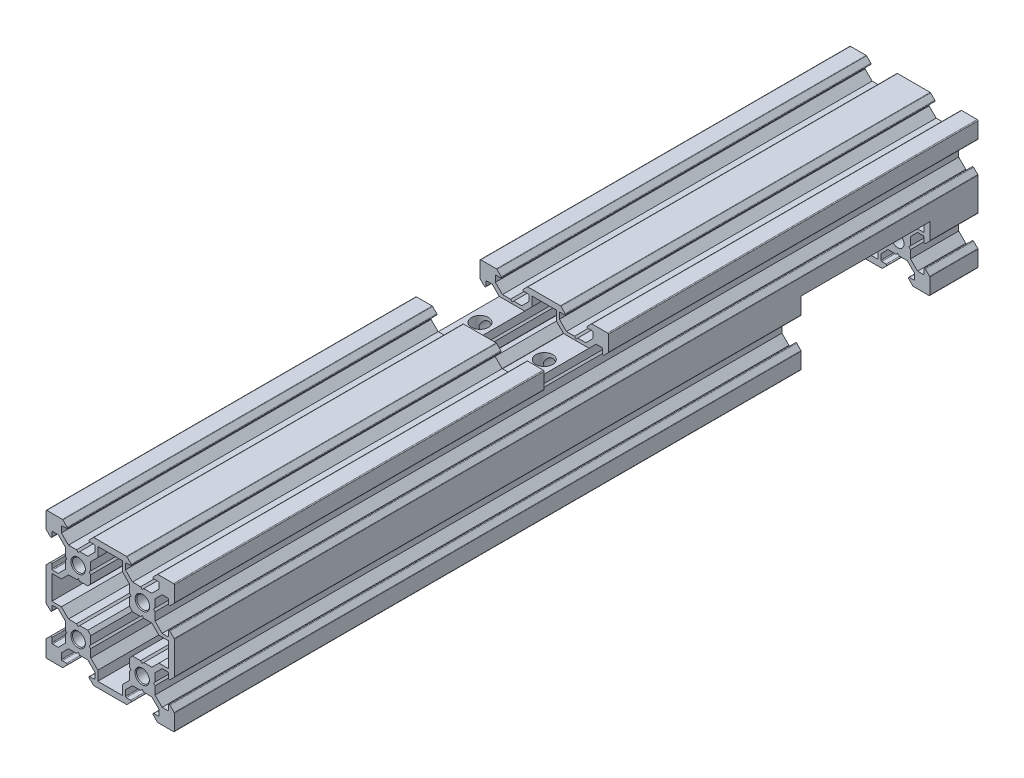
SolidWorks part; units mm, degrees
other "Marca1"
sketch "Croquis18" plane through (9.9172, 24.3141, -145) normal (0.9987, 0.0504, -0.0013) x (-0.0087, 0.1472, -0.9891)
ref_plane "Alzado" through (0, 0, 0) normal (0, 0, 1) x (1, 0, 0)
ref_plane "Planta" through (0, 0, 0) normal (0, 1, 0) x (1, 0, 0)
ref_plane "Vista lateral" through (0, 0, 0) normal (1, 0, 0) x (0, 0, -1)
sketch "Croquis1" plane through (0, 0, 0) normal (0, 0, 1) x (1, 0, 0)
  line L0 (-25.2101, -6.2) -> (-28.2, -6.2)
  line L1 (-13.8828, 8.2) -> (-6.2, 8.2)
  line L4 (-4.8096, 9.9268) -> (-3.5096, 8.6268)
  line L5 (-3.6864, 8.2) -> (-5.0429, 8.2)
  line L6 (-5.2929, 7.95) -> (-5.2929, 6.2)
  line L13 (-14.8728, 8.2) -> (-16.6, 8.2)
  line L14 (-5.2929, 6.2) -> (-3.0929, 4)
  line L15 (-3.0929, 4) -> (-0.5828, 4)
  line L16 (-16.0828, 0.5) -> (-16.5828, 0)
  line L17 (-16.0828, 3.0101) -> (-16.0828, 0.5)
  line L18 (-13.8828, 5.2101) -> (-16.0828, 3.0101)
  line L19 (-13.8828, 8.2) -> (-13.8828, 5.2101)
  line L23 (-16.0828, -3.0101) -> (-16.0828, -0.5)
  line L24 (-16.0828, -0.5) -> (-16.5828, 0)
  line L29 (-0.5828, 4) -> (-0.0828, 3.5)
  line L30 (-0.0828, 3.5) -> (0.4172, 4)
  line L31 (0.4172, 4) -> (2.9272, 4)
  line L32 (2.9272, 4) -> (5.1272, 6.2)
  line L33 (5.1272, 6.2) -> (5.1272, 7.95)
  line L34 (4.8772, 8.2) -> (3.5207, 8.2)
  line L35 (3.3439, 8.6268) -> (4.6439, 9.9268)
  line L36 (4.8207, 10) -> (9.6672, 10)
  line L37 (9.9172, 9.75) -> (9.9172, 4.9036)
  line L38 (9.8439, 4.7268) -> (8.5439, 3.4268)
  line L39 (8.1172, 3.6036) -> (8.1172, 4.9601)
  line L40 (7.8672, 5.2101) -> (6.1172, 5.2101)
  line L41 (6.1172, 5.2101) -> (3.9172, 3.0101)
  line L42 (3.9172, 3.0101) -> (3.9172, 0.5)
  line L43 (3.9172, 0.5) -> (3.4172, 0)
  line L44 (3.4172, 0) -> (3.9172, -0.5)
  line L45 (3.9172, -0.5) -> (3.9172, -3.0101)
  line L46 (3.9172, -3.0101) -> (6.1172, -5.2101)
  line L47 (6.1172, -5.2101) -> (7.8672, -5.2101)
  line L48 (8.1172, -4.9601) -> (8.1172, -3.6036)
  line L49 (8.5439, -3.4268) -> (9.8439, -4.7268)
  line L55 (5.1272, -6.2) -> (2.9272, -4)
  line L56 (2.9272, -4) -> (0.4172, -4)
  line L57 (0.4172, -4) -> (-0.0828, -3.5)
  line L58 (-0.0828, -3.5) -> (-0.5828, -4)
  line L59 (-0.5828, -4) -> (-3.0929, -4)
  line L66 (-4, -3.0101) -> (-4, -0.5)
  line L67 (-4, -0.5) -> (-3.5, 0)
  line L68 (-4, 0.5) -> (-3.5, 0)
  line L69 (-4, 3.0101) -> (-4, 0.5)
  line L70 (-6.2, 5.2101) -> (-4, 3.0101)
  line L71 (-6.2, 8.2) -> (-6.2, 5.2101)
  line L72 (-16.9899, -4) -> (-16.0828, -3.0101)
  line L78 (-4, -3.0101) -> (-3.0929, -4)
  line L164 (-26.2, 5.2101) -> (-24, 3.0101)
  line L165 (-24, 3.0101) -> (-24, 0.5)
  line L166 (-24, 0.5) -> (-23.5, 0)
  line L167 (-23.5, 0) -> (-24, -0.5)
  line L168 (-24, -0.5) -> (-24, -3.0101)
  line L169 (-24, -3.0101) -> (-26.2, -5.2101)
  line L170 (-26.2, -5.2101) -> (-27.95, -5.2101)
  line L171 (-28.2, -4.9601) -> (-28.2, -3.6036)
  line L172 (-28.6268, -3.4268) -> (-29.9268, -4.7268)
  line L178 (-25.2101, -6.2) -> (-23.0101, -4)
  line L179 (-23.0101, -4) -> (-20.5, -4)
  line L180 (-20.5, -4) -> (-20, -3.5)
  line L181 (-20, -3.5) -> (-19.5, -4)
  line L182 (-19.5, -4) -> (-16.9899, -4)
  line L228 (-4.9864, 10) -> (-15.0964, 10)
  line L229 (-15.2732, 9.9268) -> (-16.5732, 8.6268)
  line L230 (-16.3964, 8.2) -> (-15.0399, 8.2)
  line L231 (-14.7899, 7.95) -> (-14.7899, 6.2)
  line L232 (-14.7899, 6.2) -> (-16.9899, 4)
  line L233 (-16.9899, 4) -> (-19.5, 4)
  line L234 (-19.5, 4) -> (-20, 3.5)
  line L235 (-20, 3.5) -> (-20.5, 4)
  line L236 (-20.5, 4) -> (-23.0101, 4)
  line L237 (-23.0101, 4) -> (-25.2101, 6.2)
  line L238 (-25.2101, 6.2) -> (-25.2101, 7.95)
  line L239 (-24.9601, 8.2) -> (-23.6036, 8.2)
  line L240 (-23.4268, 8.6268) -> (-24.7268, 9.9268)
  line L241 (-24.9036, 10) -> (-29.75, 10)
  line L242 (-30, 9.75) -> (-30, 4.9036)
  line L243 (-29.9268, 4.7268) -> (-28.6268, 3.4268)
  line L244 (-28.2, 3.6036) -> (-28.2, 4.9601)
  line L245 (-27.95, 5.2101) -> (-26.2, 5.2101)
  line L256 (-29.9268, 0) -> (13.1752, 0) construction
  line L257 (-29.75, -19.9172) -> (9.6672, -19.9172) construction
  line L258 (-20, 14.7068) -> (-20, -27.5583) construction
  line L259 (-40.4121, -9.9586) -> (29.5949, -9.9586) construction
  line L260 (-0.0828, 12.632) -> (-0.0828, -27.5583) construction
  line L261 (-10.0414, -36.5607) -> (-10.0414, 12.632) construction
  line L262 (-30, -4.9036) -> (-30, -6.2)
  line L265 (9.9172, -6.2) -> (9.9172, -4.9036)
  line L267 (5.1272, -13.7172) -> (2.9272, -15.9172)
  line L268 (2.9272, -15.9172) -> (0.4172, -15.9172)
  line L269 (0.4172, -15.9172) -> (-0.0828, -16.4172)
  line L270 (-0.0828, -16.4172) -> (-0.5828, -15.9172)
  line L271 (-0.5828, -15.9172) -> (-3.0929, -15.9172)
  line L272 (-4, -16.9071) -> (-3.0929, -15.9172)
  line L273 (-4, -16.9071) -> (-4, -19.4172)
  line L274 (-4, -19.4172) -> (-3.5, -19.9172)
  line L275 (-4, -20.4172) -> (-3.5, -19.9172)
  line L276 (-4, -22.9272) -> (-4, -20.4172)
  line L277 (-6.2, -25.1272) -> (-4, -22.9272)
  line L278 (-6.2, -28.1172) -> (-6.2, -25.1272)
  line L279 (-13.8828, -28.1172) -> (-6.2, -28.1172)
  line L280 (-13.8828, -28.1172) -> (-13.8828, -25.1272)
  line L281 (-13.8828, -25.1272) -> (-16.0828, -22.9272)
  line L282 (-16.0828, -22.9272) -> (-16.0828, -20.4172)
  line L283 (-16.0828, -20.4172) -> (-16.5828, -19.9172)
  line L284 (-16.0828, -19.4172) -> (-16.5828, -19.9172)
  line L285 (-16.0828, -16.9071) -> (-16.0828, -19.4172)
  line L286 (-16.9899, -15.9172) -> (-16.0828, -16.9071)
  line L287 (-19.5, -15.9172) -> (-16.9899, -15.9172)
  line L288 (-20, -16.4172) -> (-19.5, -15.9172)
  line L289 (-20.5, -15.9172) -> (-20, -16.4172)
  line L290 (-23.0101, -15.9172) -> (-20.5, -15.9172)
  line L291 (-25.2101, -13.7172) -> (-23.0101, -15.9172)
  line L292 (-25.2101, -13.7172) -> (-28.2, -13.7172)
  line L294 (-30, -15.0136) -> (-30, -13.7172)
  line L295 (-28.6268, -16.4904) -> (-29.9268, -15.1904)
  line L296 (-28.2, -14.9571) -> (-28.2, -16.3136)
  line L297 (-26.2, -14.7071) -> (-27.95, -14.7071)
  line L298 (-24, -16.9071) -> (-26.2, -14.7071)
  line L299 (-24, -19.4172) -> (-24, -16.9071)
  line L300 (-23.5, -19.9172) -> (-24, -19.4172)
  line L301 (-24, -20.4172) -> (-23.5, -19.9172)
  line L302 (-24, -22.9272) -> (-24, -20.4172)
  line L303 (-26.2, -25.1272) -> (-24, -22.9272)
  line L304 (-27.95, -25.1272) -> (-26.2, -25.1272)
  line L305 (-28.2, -23.5207) -> (-28.2, -24.8772)
  line L306 (-29.9268, -24.6439) -> (-28.6268, -23.3439)
  line L307 (-30, -29.6672) -> (-30, -24.8207)
  line L308 (-24.9036, -29.9172) -> (-29.75, -29.9172)
  line L309 (-23.4268, -28.5439) -> (-24.7268, -29.8439)
  line L310 (-24.9601, -28.1172) -> (-23.6036, -28.1172)
  line L311 (-25.2101, -26.1172) -> (-25.2101, -27.8672)
  line L312 (-23.0101, -23.9172) -> (-25.2101, -26.1172)
  line L313 (-20.5, -23.9172) -> (-23.0101, -23.9172)
  line L314 (-20, -23.4172) -> (-20.5, -23.9172)
  line L315 (-19.5, -23.9172) -> (-20, -23.4172)
  line L316 (-16.9899, -23.9172) -> (-19.5, -23.9172)
  line L317 (-14.7899, -26.1172) -> (-16.9899, -23.9172)
  line L318 (-14.7899, -27.8672) -> (-14.7899, -26.1172)
  line L319 (-16.3964, -28.1172) -> (-15.0399, -28.1172)
  line L320 (-15.2732, -29.8439) -> (-16.5732, -28.5439)
  line L321 (-4.9864, -29.9172) -> (-15.0964, -29.9172)
  line L322 (-4.8096, -29.8439) -> (-3.5096, -28.5439)
  line L323 (-3.6864, -28.1172) -> (-5.0429, -28.1172)
  line L324 (-5.2929, -27.8672) -> (-5.2929, -26.1172)
  line L325 (-5.2929, -26.1172) -> (-3.0929, -23.9172)
  line L326 (-3.0929, -23.9172) -> (-0.5828, -23.9172)
  line L327 (-0.5828, -23.9172) -> (-0.0828, -23.4172)
  line L328 (-0.0828, -23.4172) -> (0.4172, -23.9172)
  line L329 (0.4172, -23.9172) -> (2.9272, -23.9172)
  line L330 (2.9272, -23.9172) -> (5.1272, -26.1172)
  line L331 (5.1272, -26.1172) -> (5.1272, -27.8672)
  line L332 (4.8772, -28.1172) -> (3.5207, -28.1172)
  line L333 (3.3439, -28.5439) -> (4.6439, -29.8439)
  line L334 (4.8207, -29.9172) -> (9.6672, -29.9172)
  line L335 (9.9172, -29.6672) -> (9.9172, -24.8207)
  line L336 (9.8439, -24.6439) -> (8.5439, -23.3439)
  line L337 (8.1172, -23.5207) -> (8.1172, -24.8772)
  line L338 (7.8672, -25.1272) -> (6.1172, -25.1272)
  line L339 (6.1172, -25.1272) -> (3.9172, -22.9272)
  line L340 (3.9172, -22.9272) -> (3.9172, -20.4172)
  line L341 (3.9172, -20.4172) -> (3.4172, -19.9172)
  line L342 (3.4172, -19.9172) -> (3.9172, -19.4172)
  line L343 (3.9172, -19.4172) -> (3.9172, -16.9071)
  line L344 (3.9172, -16.9071) -> (6.1172, -14.7071)
  line L345 (6.1172, -14.7071) -> (7.8672, -14.7071)
  line L346 (8.1172, -14.9571) -> (8.1172, -16.3136)
  line L347 (8.5439, -16.4904) -> (9.8439, -15.1904)
  line L348 (9.9172, -13.7172) -> (9.9172, -15.0136)
  line L349 (5.1272, -13.7172) -> (8.1172, -13.7172)
  line L350 (5.1272, -6.2) -> (8.1172, -6.2)
  line L351 (8.1172, -6.2) -> (8.1172, -13.7172)
  line L352 (9.9172, -13.7172) -> (9.9172, -6.2)
  line L353 (-30, -6.2) -> (-30, -13.7172)
  line L354 (-28.2, -13.7172) -> (-28.2, -6.2)
  arc A0 (-3.5096, 8.6268) -> (-3.6864, 8.2) centre (-3.6864, 8.45) cw
  arc A1 (-15.0964, 10) -> (-15.2732, 9.9268) centre (-15.0964, 9.75) ccw
  arc A2 (-15.0399, 8.2) -> (-14.7899, 7.95) centre (-15.0399, 7.95) cw
  arc A4 (-16.5732, 8.6268) -> (-16.3964, 8.2) centre (-16.3964, 8.45) ccw
  arc A13 (-29.9268, -4.7268) -> (-30, -4.9036) centre (-29.75, -4.9036) ccw
  arc A14 (-28.2, -3.6036) -> (-28.6268, -3.4268) centre (-28.45, -3.6036) ccw
  arc A15 (-27.95, -5.2101) -> (-28.2, -4.9601) centre (-27.95, -4.9601) cw
  arc A16 (-24.7268, 9.9268) -> (-24.9036, 10) centre (-24.9036, 9.75) ccw
  arc A17 (-23.6036, 8.2) -> (-23.4268, 8.6268) centre (-23.6036, 8.45) ccw
  arc A18 (-25.2101, 7.95) -> (-24.9601, 8.2) centre (-24.9601, 7.95) cw
  arc A19 (-28.2, 4.9601) -> (-27.95, 5.2101) centre (-27.95, 4.9601) cw
  arc A20 (-28.6268, 3.4268) -> (-28.2, 3.6036) centre (-28.45, 3.6036) ccw
  arc A21 (-30, 4.9036) -> (-29.9268, 4.7268) centre (-29.75, 4.9036) ccw
  arc A22 (-29.75, 10) -> (-30, 9.75) centre (-29.75, 9.75) ccw
  arc A23 (-5.0429, 8.2) -> (-5.2929, 7.95) centre (-5.0429, 7.95) ccw
  arc A24 (5.1272, 7.95) -> (4.8772, 8.2) centre (4.8772, 7.95) ccw
  arc A25 (3.5207, 8.2) -> (3.3439, 8.6268) centre (3.5207, 8.45) cw
  arc A26 (4.6439, 9.9268) -> (4.8207, 10) centre (4.8207, 9.75) cw
  arc A27 (9.6672, 10) -> (9.9172, 9.75) centre (9.6672, 9.75) cw
  arc A28 (9.9172, 4.9036) -> (9.8439, 4.7268) centre (9.6672, 4.9036) cw
  arc A29 (8.5439, 3.4268) -> (8.1172, 3.6036) centre (8.3672, 3.6036) cw
  arc A30 (8.1172, 4.9601) -> (7.8672, 5.2101) centre (7.8672, 4.9601) ccw
  arc A31 (7.8672, -5.2101) -> (8.1172, -4.9601) centre (7.8672, -4.9601) ccw
  arc A32 (8.1172, -3.6036) -> (8.5439, -3.4268) centre (8.3672, -3.6036) cw
  arc A33 (9.8439, -4.7268) -> (9.9172, -4.9036) centre (9.6672, -4.9036) cw
  arc A41 (-4.9864, 10) -> (-4.8096, 9.9268) centre (-4.9864, 9.75) cw
  arc A42 (-29.9268, -15.1904) -> (-30, -15.0136) centre (-29.75, -15.0136) cw
  arc A43 (-28.2, -16.3136) -> (-28.6268, -16.4904) centre (-28.45, -16.3136) cw
  arc A44 (-27.95, -14.7071) -> (-28.2, -14.9571) centre (-27.95, -14.9571) ccw
  arc A45 (-28.2, -24.8772) -> (-27.95, -25.1272) centre (-27.95, -24.8772) ccw
  arc A46 (-28.6268, -23.3439) -> (-28.2, -23.5207) centre (-28.45, -23.5207) cw
  arc A47 (-30, -24.8207) -> (-29.9268, -24.6439) centre (-29.75, -24.8207) cw
  arc A48 (-29.75, -29.9172) -> (-30, -29.6672) centre (-29.75, -29.6672) cw
  arc A49 (-24.7268, -29.8439) -> (-24.9036, -29.9172) centre (-24.9036, -29.6672) cw
  arc A50 (-23.6036, -28.1172) -> (-23.4268, -28.5439) centre (-23.6036, -28.3672) cw
  arc A51 (-25.2101, -27.8672) -> (-24.9601, -28.1172) centre (-24.9601, -27.8672) ccw
  arc A52 (-15.0399, -28.1172) -> (-14.7899, -27.8672) centre (-15.0399, -27.8672) ccw
  arc A53 (-16.5732, -28.5439) -> (-16.3964, -28.1172) centre (-16.3964, -28.3672) cw
  arc A54 (-15.0964, -29.9172) -> (-15.2732, -29.8439) centre (-15.0964, -29.6672) cw
  arc A55 (-4.9864, -29.9172) -> (-4.8096, -29.8439) centre (-4.9864, -29.6672) ccw
  arc A56 (-3.5096, -28.5439) -> (-3.6864, -28.1172) centre (-3.6864, -28.3672) ccw
  arc A57 (-5.0429, -28.1172) -> (-5.2929, -27.8672) centre (-5.0429, -27.8672) cw
  arc A58 (5.1272, -27.8672) -> (4.8772, -28.1172) centre (4.8772, -27.8672) cw
  arc A59 (3.5207, -28.1172) -> (3.3439, -28.5439) centre (3.5207, -28.3672) ccw
  arc A60 (4.6439, -29.8439) -> (4.8207, -29.9172) centre (4.8207, -29.6672) ccw
  arc A61 (9.6672, -29.9172) -> (9.9172, -29.6672) centre (9.6672, -29.6672) ccw
  arc A62 (9.9172, -24.8207) -> (9.8439, -24.6439) centre (9.6672, -24.8207) ccw
  arc A63 (8.5439, -23.3439) -> (8.1172, -23.5207) centre (8.3672, -23.5207) ccw
  arc A64 (8.1172, -24.8772) -> (7.8672, -25.1272) centre (7.8672, -24.8772) cw
  arc A65 (7.8672, -14.7071) -> (8.1172, -14.9571) centre (7.8672, -14.9571) cw
  arc A66 (8.1172, -16.3136) -> (8.5439, -16.4904) centre (8.3672, -16.3136) ccw
  arc A67 (9.8439, -15.1904) -> (9.9172, -15.0136) centre (9.6672, -15.0136) ccw
  point P134 (-10.0414, 8.2)
  dimension "D1" = 0.25
  dimension "D2" = 7.6828
  dimension "D3" = 10.1101
  dimension "D4" = 19.9172
  dimension "D5" = 19.9172
  dimension "D6" = 9.9586
  dimension "D7" = 9.9586
extrude "Saliente-Extruir1" add sketch "Croquis1" along normal blind 125 and the other way blind 125 contours A41 L228 L1 L71 L70 L69 L68 L67 L66 L23 L24 L16 L17 L18 L19 A1 L229 A4 L13 A2 L231 L232 L233 L234 L235 L236 L237 L238 A18 L239 A17 L240 A16 L241 A22 L242 A21 L243 A20 L244 region at (-4.5588, 8.8776, 0)
sketch "Croquis4" plane through (0, 0, 125) normal (0, 0, 1) x (1, 0, 0)
  line L0 (-24.6708, 0) -> (6.8007, 0) construction
  line L1 (-20, 3.5) -> (-20, 0) construction
  line L2 (-24.6708, -19.9172) -> (-20, -19.9172) construction
  line L3 (-20, -19.9172) -> (-20, -16.4172) construction
  line L4 (-0.0828, -16.4172) -> (-0.0828, -19.9172) construction
  line L5 (-0.0828, -19.9172) -> (3.4172, -19.9172) construction
  circle A0 centre (-20, 0) radius 2
  circle A1 centre (0, 0) radius 2
  circle A2 centre (-0.0828, -19.9172) radius 2
  circle A3 centre (-20, -19.9172) radius 2
  dimension "D1" = 4
extrude "Cortar-Extruir1" cut sketch "Croquis4" against normal through all
chamfer "Chaflán1" distance 0.25 angle 45 8 edges at (-18, 0, -125) (-18, -19.9172, -125) (2, 0, -125) (1.9172, -19.9172, -125) (1.9172, -19.9172, 125) (2, 0, 125) (-18, 0, 125) (-18, -19.9172, 125)
sketch "Croquis19" plane through (-30, 0, 0) normal (-1, 0, 0) x (0, 0, 1)
  line L0 (-110, -29.9172) -> (-110, -9.9172)
  line L1 (-110, -9.9172) -> (-70, -9.9172)
  line L2 (-70, -9.9172) -> (-70, -29.9172)
  line L3 (-70, -29.9172) -> (-110, -29.9172)
  line L4 (-125, -29.9172) -> (125, -29.9172) construction
  line L5 (-125, -29.6672) -> (-125, -24.8207) construction
  line L6 (-10, 10) -> (-10, 3)
  line L7 (-10, 3) -> (10, 3)
  line L8 (10, 3) -> (10, 10)
  line L9 (10, 10) -> (-10, 10)
  line L10 (-125, 10) -> (125, 10) construction
  line L11 (-125, 9.75) -> (-125, 4.9036) construction
  dimension "D1" = 20
  dimension "D2" = 15
  dimension "D3" = 40
  dimension "D4" = 115
  dimension "D5" = 20
  dimension "D6" = 7
extrude "Cortar-Extruir2" cut sketch "Croquis19" against normal through all contours L3 L0 L1 L2 | L9 L6 L7 L8
sketch "Croquis20" plane through (0, 10, 0) normal (0, 1, 0) x (1, 0, 0)
  line L0 (-20, 125) -> (-20, 10) construction
  line L1 (-16.9899, 125) -> (-19.5, 125) construction
  circle A0 centre (-20, 67) radius 1.25
  point P0 (-20, 67)
  dimension "D2" = 2.5
  dimension "D1" = 58
extrude "Cortar-Extruir3" cut sketch "Croquis20" against normal through all
sketch "Croquis21" plane through (0, -29.9172, 0) normal (0, -1, 0) x (1, 0, 0)
  line L0 (-20, -65.75) -> (-20, 125) construction
  line L1 (-0.0828, -70) -> (-0.0828, 125) construction
  line L2 (-4.9864, 125) -> (-15.0964, 125) construction
  point P0 (-20, 0)
  point P1 (-0.0828, 0)
  dimension "D1" = 125
hole_wizard "Refrentado para tornillo con cabeza hueca de M51" positions "Croquis22" profile "Croquis23" counterbore size "M5" standard "ISO" end condition through all
sketch "Croquis22" plane through (0, -29.9172, 0) normal (0, -1, 0) x (-1, 0, 0)
  point P0 (20, 0)
  point P3 (0, 0)
sketch "Croquis23" plane through (-20, -29.9172, 0) normal (1, 0, 0) x (0, 0, -1)
  line L0 (0, 0) -> (0, 39.9172)
  line L1 (0, 39.9172) -> (2.65, 39.9172)
  line L3 (2.65, 39.9172) -> (2.65, 5.4)
  line L4 (2.65, 5.4) -> (5, 5.4)
  line L5 (5, 5.4) -> (5, 0)
  line L7 (5, 0) -> (0, 0)
  line L11 (0, -6.35) -> (0, 107.95) construction
  dimension "Diámetro de taladro hasta el siguiente" = 5.3
  dimension "Profundidad de taladro hasta el siguiente" = 39.9172
  dimension "Diámetro de refrentado" = 10
  dimension "Profundidad de refrentado" = 5.4
ref_plane "Plano1" through (0, -29.9172, 0) normal (0, -1, 0) x (-1, 0, 0)
ref_plane "Plano2" through (-30, 0, 0) normal (-1, 0, 0) x (0, 0, 1)
ref_plane "Plano3" through (0, 10, 0) normal (0, 1, 0) x (1, 0, 0)
ref_plane "Plano4" through (9.9172, 0, 0) normal (1, 0, 0) x (0, 0, -1)
